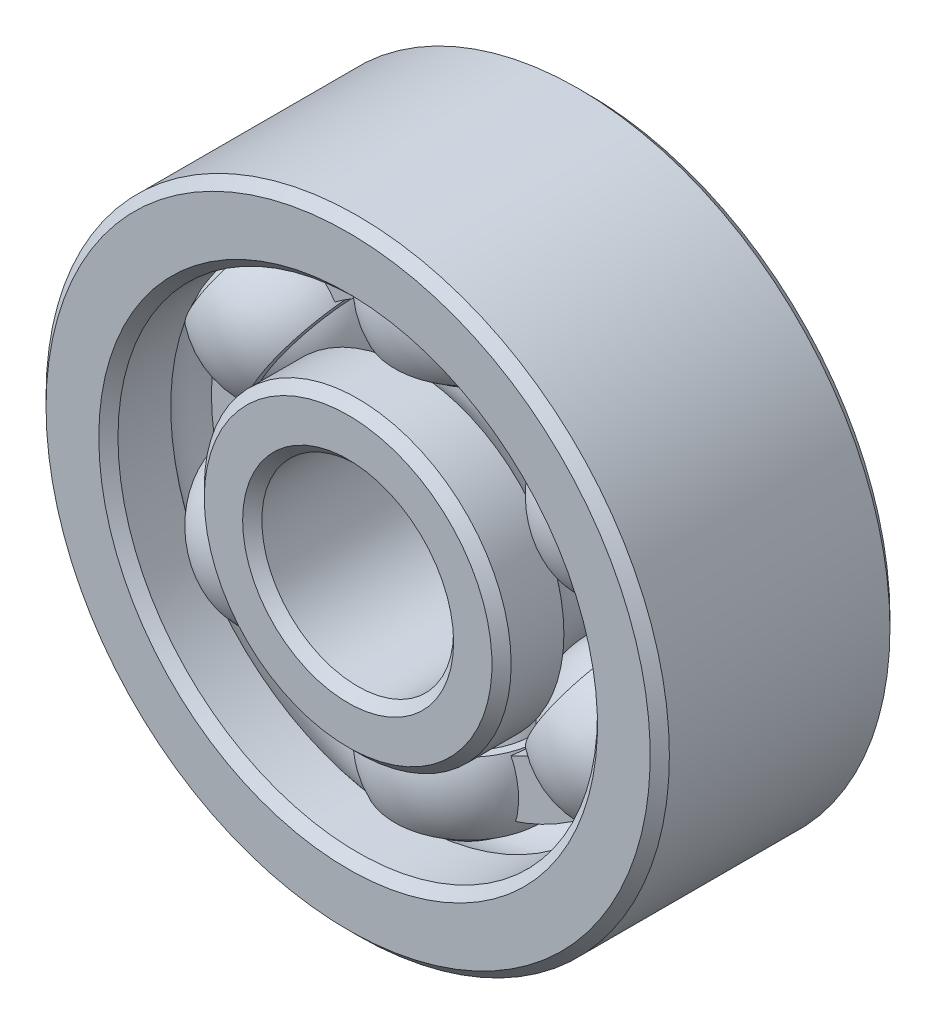
SolidWorks part; units mm, degrees
material "Alloy Steel"
ref_plane "Front" through (0, 0, 0) normal (0, 0, 1) x (1, 0, 0)
ref_plane "Top" through (0, 0, 0) normal (0, 1, 0) x (1, 0, 0)
ref_plane "Right" through (0, 0, 0) normal (1, 0, 0) x (0, 0, -1)
ref_axis "Ось1" through (0, 0, -80.9) along (0, 0, 1)
sketch "Sketch1" plane through (0, 0, 0) normal (1, 0, 0) x (0, 0, -1)
  line L0 (0, 6.5) -> (0, 0) construction
  line L1 (-2.5, 6.5) -> (2.5, 6.5)
  line L2 (-2.5, 6.5) -> (-2.5, 5)
  line L3 (-2.5, 5) -> (-1.2, 5)
  line L4 (2.5, 6.5) -> (2.5, 5)
  line L5 (-2.5, 3.2) -> (-1.2, 3.2)
  line L6 (-2.5, 3.2) -> (-2.5, 2)
  line L7 (-2.5, 2) -> (2.5, 2)
  line L8 (2.5, 3.2) -> (2.5, 2)
  line L9 (-2.5, 5) -> (2.5, 3.2) construction
  line L10 (2.5, 5) -> (-2.5, 3.2) construction
  line L11 (1.2, 5) -> (2.5, 5)
  line L12 (1.2, 3.2) -> (2.5, 3.2)
  line L13 (0, 0) -> (2.5, 0) construction
  arc A0 (1.2, 5) -> (-1.2, 5) centre (0, 4.1) ccw
  arc A1 (-1.2, 3.2) -> (1.2, 3.2) centre (0, 4.1) ccw
  dimension "D7" = 1.5
  dimension "D1" = 1.2
  dimension "D2" = 1.5
  dimension "D3" = 4
  dimension "D4" = 13
  dimension "D5" = 5
  dimension "D6" = 1.8
sketch "Sketch2" plane through (0, 0, 0) normal (1, 0, 0) x (0, 0, -1)
  line L0 (0, 2.5873) -> (0, 5.6127)
  arc A0 (0, 2.6) -> (0, 5.6) centre (0, 4.1) ccw construction
  arc A1 (1.2, 5) -> (-1.2, 5) centre (0, 4.1) ccw construction
  arc A2 (0, 2.5873) -> (0, 5.6127) centre (0, 4.1) ccw
  dimension "D1" = 0.0127
sketch "Sketch3" plane through (0, 0, 0) normal (1, 0, 0) x (0, 0, -1)
  line L4 (1.3565, 3.35) -> (1.5256, 3.35)
  line L6 (1.2, 3.2) -> (2.5, 3.2) construction
  line L7 (1.3565, 4.85) -> (1.5256, 4.85)
  line L8 (1.2, 5) -> (2.5, 5) construction
  arc A0 (1.5256, 3.35) -> (1.5256, 4.85) centre (0, 4.1) ccw
  arc A2 (1.2, 5) -> (-1.2, 5) centre (0, 4.1) ccw construction
  arc A3 (1.3565, 3.35) -> (1.3565, 4.85) centre (0, 4.1) ccw
  dimension "D2" = 0.05
  dimension "D4" = 0.15
  dimension "D5" = 0.15
revolve "Revolve1" add sketch "Sketch1" angle 360 about L13
revolve "Revolve2" add sketch "Sketch2" angle 360 about L0
pattern_circular "CirPattern1" count 6 over 360 about axis through (0, 0, 0) along (0, 0, 1) of bodies 104
revolve "Revolve3" add sketch "Sketch3" angle 360 about L0
pattern_circular "CirPattern2" count 6 over 360 about axis through (0, 0, 0) along (0, 0, 1) of bodies 112
sketch "Sketch5" plane through (0, 0, 0) normal (0, 0, 1) x (1, 0, 0)
  circle A0 centre (0, 0) radius 3.2 construction
  circle A2 centre (0, 0) radius 3.2 construction
  circle A3 centre (0, 0) radius 5 construction
  arc A4 (-1.4343, 4.5807) -> (-3.2499, 3.5325) centre (0, 0) ccw
  arc A5 (-1.3613, 3.4405) -> (-2.2988, 2.8992) centre (0, 0) ccw
  circle A6 centre (-3.5507, 2.05) radius 1.5127 construction
  circle A7 centre (0, 4.1) radius 1.5127 construction
  arc A8 (-2.2988, 2.8992) -> (-3.2499, 3.5325) centre (-3.5507, 2.05) ccw
  arc A9 (-1.4343, 4.5807) -> (-1.3613, 3.4405) centre (0, 4.1) ccw
  circle A10 centre (0, 0) radius 4.8 construction
  circle A11 centre (0, 0) radius 3.7 construction
  circle A13 centre (0, 0) radius 5 construction
  dimension "D1" = 0.2
  dimension "D2" = 0.5
extrude "Extrude1" add sketch "Sketch5" along normal mid plane 1.1 separate body
pattern_circular "CirPattern4" count 6 over 360 about axis through (0, 0, 0) along (0, 0, -1) reverse direction yes of bodies 154
chamfer "Chamfer1" distance 0.2 angle 45 4 edges at (2, 0, -2.5) (3.2, 0, -2.5) (3.2, 0, 2.5) (2, 0, 2.5)
chamfer "Фаска1" distance 0.2 angle 45 4 edges at (6.5, 0, 2.5) (5, 0, 2.5) (5, 0, -2.5) (6.5, 0, -2.5)
